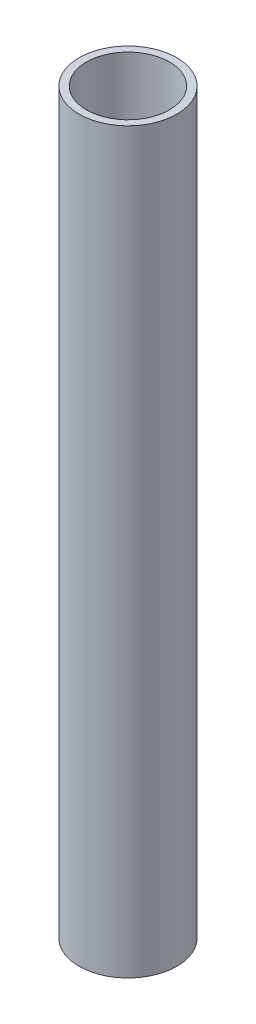
SolidWorks part; units mm, degrees
ref_plane "Front Plane" through (0, 0, 0) normal (0, 0, 1) x (1, 0, 0)
ref_plane "Top Plane" through (0, 0, 0) normal (0, 1, 0) x (1, 0, 0)
ref_plane "Right Plane" through (0, 0, 0) normal (1, 0, 0) x (0, 0, -1)
sketch "Sketch1" plane through (0, 0, 0) normal (0, 1, 0) x (1, 0, 0)
  circle A0 centre (0, 0) radius 3.975
  dimension "D1" = 7.95
extrude "Boss-Extrude1" add sketch "Sketch1" along normal blind 60
ref_plane "Plane1" through (0, 25, 0) normal (0, 1, 0) x (1, 0, 0)
sketch "Sketch2" plane through (0, 25, 0) normal (0, 1, 0) x (1, 0, 0)
  circle A2 centre (0, 0) radius 3.375
  circle A3 centre (0, 0) radius 3.375
  dimension "D1" = 0.6
extrude "Cut-Extrude1" cut sketch "Sketch2" along normal through all
sketch "Sketch3" plane through (0, 0, 0) normal (1, 0, 0) x (0, 0, -1)
  line L7 (0, 27.475) -> (0, 31) construction
  line L8 (-2.475, 27.475) -> (-2.475, 31)
  line L9 (2.475, 27.475) -> (2.475, 31)
  line L10 (4.3725, 25) -> (-4.3725, 25) construction
  line L11 (-3.975, 60) -> (-3.975, 0) construction
  arc A0 (-2.475, 27.475) -> (2.475, 27.475) centre (0, 27.475) ccw
  arc A1 (2.475, 31) -> (-2.475, 31) centre (0, 31) ccw
  point P2 (0, 29.2375)
  dimension "D2" = 6
  dimension "D4" = 3.525
  dimension "D1" = 1.5
  dimension "D3" = 4.95
extrude "Cut-Extrude2" cut sketch "Sketch3" against normal through all
sketch "Sketch4" plane through (0, 25, 0) normal (0, 1, 0) x (1, 0, 0)
  circle A2 centre (0, 0) radius 3.375
  circle A3 centre (0, 0) radius 3.375
  dimension "D1" = 0
curve "Helix/Spiral1" pitch 100 height 100 turns 1
sketch "Sketch5" plane through (0, 25, 0) normal (0, 1, 0) x (1, 0, 0)
  line L0 (0.8735, 3.26) -> (0.8541, 3.1876)
  line L1 (-0.8735, 3.26) -> (-0.8541, 3.1876)
  line L2 (0, 0) -> (4.6731, 0) construction
  line L3 (0, 0) -> (0, 4.6971) construction
  line L4 (3.3704, 0.1766) -> (3.2955, 0.1727)
  line L5 (2.8305, 1.8382) -> (2.7676, 1.7973)
  line L6 (1.2095, -3.1508) -> (1.1826, -3.0808)
  line L7 (2.6229, -2.124) -> (2.5646, -2.0768)
  line L8 (-2.6229, -2.124) -> (-2.5646, -2.0768)
  line L9 (-1.2095, -3.1508) -> (-1.1826, -3.0808)
  line L10 (-2.8305, 1.8382) -> (-2.7676, 1.7973)
  line L11 (-3.3704, 0.1766) -> (-3.2955, 0.1727)
  arc A0 (0.8541, 3.1876) -> (-0.8541, 3.1876) centre (0, 0) ccw
  circle A2 centre (0, 0) radius 3.375
  arc A3 (0.8735, 3.26) -> (-0.8735, 3.26) centre (0, 0) ccw
  arc A4 (3.2955, 0.1727) -> (2.7676, 1.7973) centre (0, 0) ccw
  arc A5 (3.3704, 0.1766) -> (2.8305, 1.8382) centre (0, 0) ccw
  arc A6 (1.1826, -3.0808) -> (2.5646, -2.0768) centre (0, 0) ccw
  arc A7 (1.2095, -3.1508) -> (2.6229, -2.124) centre (0, 0) ccw
  arc A8 (-2.5646, -2.0768) -> (-1.1826, -3.0808) centre (0, 0) ccw
  arc A9 (-2.6229, -2.124) -> (-1.2095, -3.1508) centre (0, 0) ccw
  arc A10 (-2.7676, 1.7973) -> (-3.2955, 0.1727) centre (0, 0) ccw
  arc A11 (-2.8305, 1.8382) -> (-3.3704, 0.1766) centre (0, 0) ccw
  point P6 (2.7733, 0.8479)
  point P7 (3.3, 0)
  point P31 (0, 0)
  dimension "D3" = 30
  dimension "D4" = 75
  dimension "D1" = 0
  dimension "D2" = 5
sweep "Cut-Sweep1" [suppressed] cut profiles "Sketch5" path "Helix/Spiral1"
sketch "Sketch7" plane through (0, 0, 0) normal (0, 1, 0) x (1, 0, 0)
  circle A0 centre (0, 0) radius 2.7
  dimension "D1" = 5.4
extrude "Cut-Extrude3" cut sketch "Sketch7" along normal blind 23
